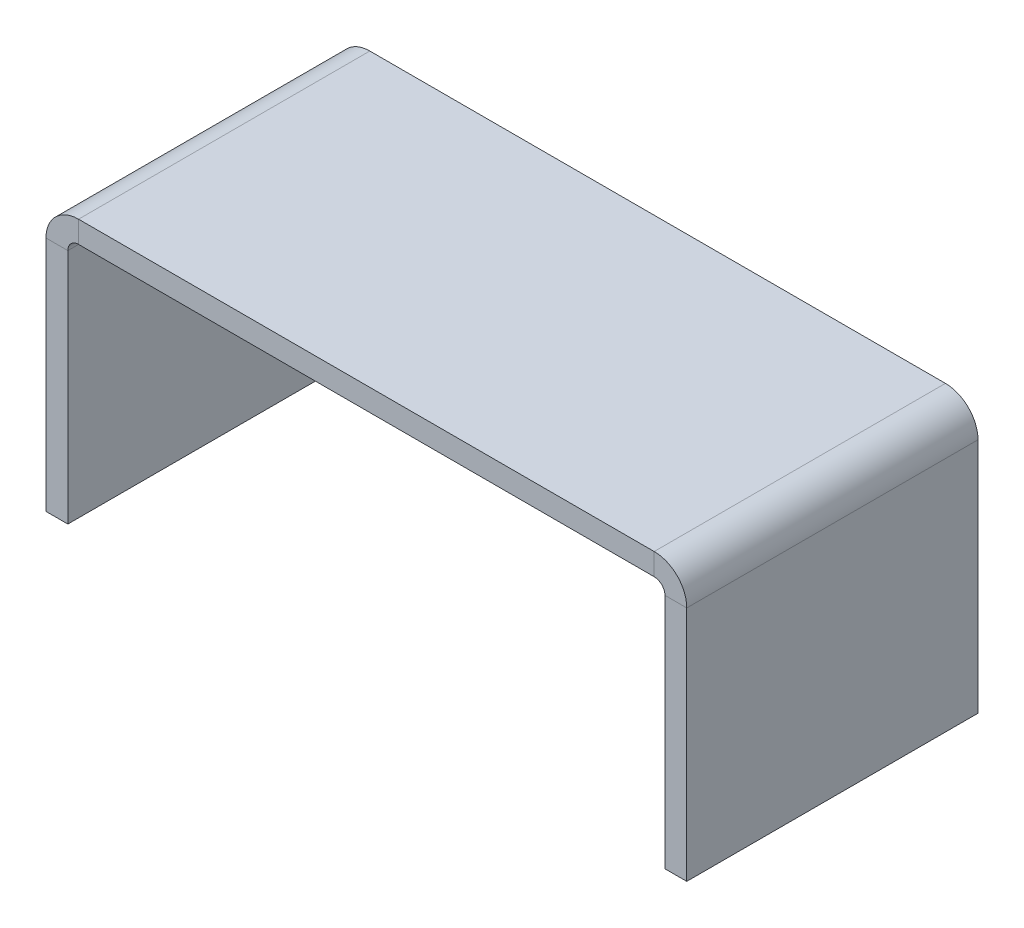
SolidWorks part; units mm, degrees
note: The reader was unsure of these and kept them because the rebuilt part matched: flange length of "Brida de arista1".
ref_plane "Alzado" through (0, 0, 0) normal (0, 0, 1) x (1, 0, 0)
ref_plane "Planta" through (0, 0, 0) normal (0, 1, 0) x (1, 0, 0)
ref_plane "Vista lateral" through (0, 0, 0) normal (1, 0, 0) x (0, 0, -1)
sketch "Croquis2" plane through (0, 0, 0) normal (0, 1, 0) x (1, 0, 0)
  line L1 (-22, -10) -> (22, -10)
  line L2 (-22, -10) -> (-22, 10)
  line L3 (-22, 10) -> (22, 10)
  line L4 (22, -10) -> (22, 10)
  line L5 (-22, -10) -> (22, 10) construction
  line L6 (-22, 10) -> (22, -10) construction
  point P0 (0, 0)
  dimension "D1" = 44
  dimension "D2" = 20
base flange "Brida base1" sketch "Croquis2" thickness 1.5 reverse thickness direction no parameters "D1"=0.7366
edge flange "Brida de arista1" sketch "Croquis11" flange profiles "Croquis11", "Croquis12" flange angle 90 flange length 18.5 flange position material inside bend radius 0.7366 thickness 1.5 relief rectangular parameters "D6"=10, "D8"=0.5
sketch "Croquis11" plane through (-22, -1.5, 0) normal (-1, 0, 0) x (0, 0, -1)
  line L2 (-10, 0) -> (-10, 17)
  line L3 (-10, 17) -> (10, 17)
  line L4 (10, 17) -> (10, 0)
  line L5 (10, 0) -> (-10, 0) construction
  line L6 (10, 0) -> (-10, 0)
sketch "Croquis12" plane through (22, -1.5, 0) normal (1, 0, 0) x (0, 0, 1)
  line L0 (10, 0) -> (-10, 0) construction
  line L1 (10, 0) -> (-10, 0)
  line L2 (-10, 0) -> (-10, 17)
  line L3 (-10, 17) -> (10, 17)
  line L4 (10, 17) -> (10, 0)
bend "Pliegue de arista1" bend radius 0.7366 bend angle 90 parameters "D5"=1
bend "Pliegue de arista2" bend radius 0.7366 bend angle 90 parameters "D5"=2
sketch "Líneas de pliegue1" [suppressed] plane through (0, 0, 0) normal (0, 1, 0) x (1, 0, 0)
sketch "Cuadro delimitador1" [suppressed] plane through (0, 0, 0) normal (0, 1, 0) x (1, 0, 0)
sheet metal parameters "Chapa metálica2" thickness 1.5 parameters "D1"=0.7366
flat pattern "Chapa desplegada2" [suppressed]
sketch "Líneas de pliegue2" plane through (0, 0, 0) normal (0, 1, 0) x (1, 0, 0)
sketch3d "Cuadro delimitador2" [suppressed]
  line L0 (-22, 10, 0) -> (22, 10, 0) construction
  line L1 (-22, -10, 0) -> (22, -10, 0) construction
  line L2 (-22, 10, 0) -> (-22, -10, 0) construction
  line L3 (22, 10, 0) -> (22, -10, 0) construction
sheet metal parameters "Chapa metálica3" thickness 1.5 parameters "D1"=0.7366
flat pattern "Chapa desplegada2"
sketch "Líneas de pliegue2" plane through (0, 0, 0) normal (0, 1, 0) x (1, 0, 0)
  line L0 (20.931, -10) -> (20.931, 10) construction
  line L1 (-20.931, 10) -> (-20.931, -10) construction
  line L2 (20.931, -10) -> (20.931, 10) construction
  line L3 (-20.931, 10) -> (-20.931, -10) construction
sketch3d "Cuadro delimitador2" [suppressed]
  line L0 (38.3619, 10, 0) -> (-38.3619, 10, 0) construction
  line L1 (38.3619, -10, 0) -> (-38.3619, -10, 0) construction
  line L2 (38.3619, 10, 0) -> (38.3619, -10, 0) construction
  line L3 (-38.3619, 10, 0) -> (-38.3619, -10, 0) construction
bend of the flat pattern "Aplanar-<Pliegue de arista1>1"
bend of the flat pattern "Aplanar-<Pliegue de arista2>1"
